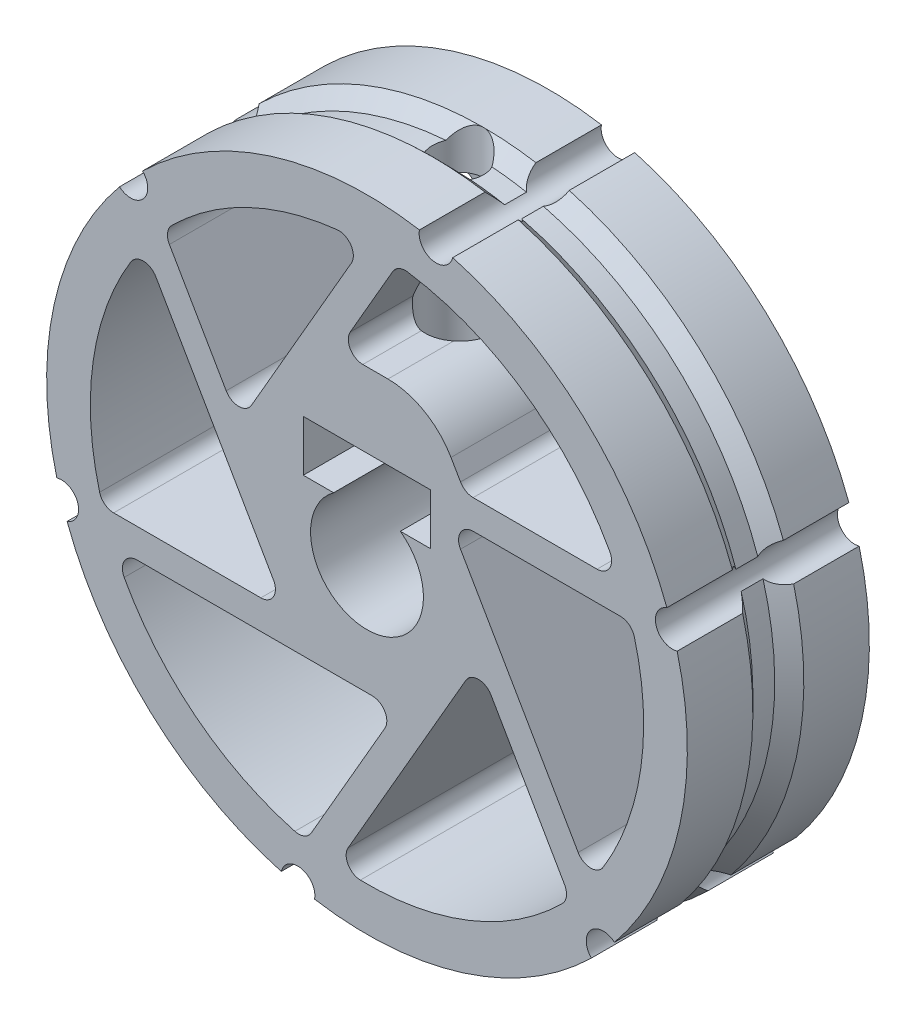
SolidWorks part; units mm, degrees
ref_plane "Front Plane" through (0, 0, 0) normal (0, 0, 1) x (1, 0, 0)
ref_plane "Top Plane" through (0, 0, 0) normal (0, 1, 0) x (1, 0, 0)
ref_plane "Right Plane" through (0, 0, 0) normal (1, 0, 0) x (0, 0, -1)
sketch "Sketch1" plane through (0, 0, 0) normal (0, 0, 1) x (1, 0, 0)
  line L0 (1.833, 2.5) -> (3.5, 2.5)
  line L1 (3.5, 2.5) -> (3.5, 5.3)
  line L2 (3.5, 5.3) -> (-3.5, 5.3)
  line L3 (-3.5, 5.3) -> (-3.5, 2.5)
  line L4 (-3.5, 2.5) -> (-1.833, 2.5)
  line L5 (-1.6583, 2.5) -> (1.6583, 2.5) construction
  line L6 (-7.0437, 0) -> (-12.2439, 9.0071)
  line L7 (3.5218, -6.1) -> (7.0437, 0) construction
  line L8 (7.0437, 0) -> (3.5218, 6.1) construction
  line L9 (3.5218, 6.1) -> (-3.5218, 6.1) construction
  line L10 (-3.5218, 6.1) -> (-7.0437, 0) construction
  line L11 (-7.0437, 0) -> (-3.5218, -6.1) construction
  line L12 (-3.5218, -6.1) -> (3.5218, -6.1) construction
  line L13 (-3.5218, -6.1) -> (-13.9223, -6.1)
  line L14 (3.5218, -6.1) -> (-1.6784, -15.1071)
  line L15 (7.0437, 0) -> (12.2439, -9.0071)
  line L16 (-6.1199, 1.6) -> (-11.1564, 10.3235) construction
  line L17 (6.1199, -1.6) -> (11.1564, -10.3235)
  line L18 (1.6743, -6.1) -> (-3.3622, -14.8235)
  line L19 (-4.4456, -4.5) -> (-14.5186, -4.5)
  line L20 (3.5218, 6.1) -> (13.9223, 6.1) construction
  line L21 (4.4456, 4.5) -> (14.5186, 4.5)
  line L22 (-11.1564, 10.3235) -> (-7.0437, 3.2)
  line L23 (-7.0437, 3.2) -> (-3.4613, 9.4048)
  line L24 (-3.4613, 9.4048) -> (3.4613, 9.4048) construction
  line L25 (3.4613, 9.4048) -> (5.3694, 6.1)
  line L26 (5.3694, 6.1) -> (13.9223, 6.1)
  line L29 (-7.0437, 0) -> (-4.4456, -4.5)
  line L30 (-3.5218, -6.1) -> (1.6743, -6.1)
  line L31 (3.5218, -6.1) -> (6.1199, -1.6)
  line L32 (7.0437, 0) -> (4.4456, 4.5)
  line L33 (-3.4613, 9.4048) -> (-0.1157, 15.1996)
  line L34 (1.6784, 15.1071) -> (-1.6138, 9.4048)
  line L35 (3.4613, 9.4048) -> (-1.6138, 9.4048)
  circle A0 centre (0, 0) radius 3 construction
  circle A1 centre (0, 0) radius 3.1 construction
  arc A2 (-1.833, 2.5) -> (1.833, 2.5) centre (0, 0) ccw
  circle A3 centre (0, 0) radius 6.1 construction
  circle A4 centre (0, 0) radius 20 construction
  circle A6 centre (0, 0) radius 17.6
  circle A7 centre (0, 0) radius 15.2 construction
  arc A8 (-0.1157, 15.1996) -> (-11.1564, 10.3235) centre (0, 0) ccw
  arc A9 (-12.2439, 9.0071) -> (-14.5186, -4.5) centre (0, 0) ccw
  arc A10 (-3.3622, -14.8235) -> (-13.9223, -6.1) centre (0, 0) cw
  arc A11 (11.1564, -10.3235) -> (-1.6784, -15.1071) centre (0, 0) cw
  arc A12 (14.5186, 4.5) -> (12.2439, -9.0071) centre (0, 0) cw
  arc A13 (13.9223, 6.1) -> (1.6784, 15.1071) centre (0, 0) ccw
  point P13 (0, -3)
  point P43 (0, 9.4048)
  point P55 (-17.6, 0)
  point P56 (17.6, 0)
  point P58 (0, -17.6)
  point P59 (0, 17.6)
  point P61 (-15.2, 0)
  dimension "D1" = 6
  dimension "D7" = 40
  dimension "D3" = 7
  dimension "D4" = 2.8
  dimension "D5" = 5.5
  dimension "D6" = 0.8
  dimension "D10" = 1.6
  dimension "D11" = 4.1048
  dimension "D12" = 1.6
  dimension "D13" = 1.6
  dimension "D2" = 0.1
  dimension "D8" = 2.4
  dimension "D9" = 2.4
extrude "Boss-Extrude1" add sketch "Sketch1" along normal blind 10
ref_axis "Axis1" through (0, 0, 10) along (0, 0, -1)
sketch "Sketch3" plane through (0, 0, 10) normal (0, 0, 1) x (1, 0, 0)
  line L0 (2.5981, -6.1) -> (-3.8016, -17.1845) construction
  line L1 (-3.5218, -6.1) -> (3.5218, -6.1) construction
  line L2 (1.6743, -6.1) -> (-3.3622, -14.8235) construction
  line L3 (1.6743, -6.1) -> (3.5218, -6.1) construction
  circle A0 centre (-3.8016, -17.1845) radius 0.937
  circle A1 centre (0, 0) radius 17.6 construction
  circle A2 centre (0, 0) radius 15.2 construction
  circle A3 centre (-16.783, -5.3) radius 0.937
  circle A4 centre (-12.9814, 11.8845) radius 0.937
  circle A5 centre (3.8016, 17.1845) radius 0.937
  circle A6 centre (16.783, 5.3) radius 0.937
  circle A7 centre (12.9814, -11.8845) radius 0.937
  point P14 (2.5981, -6.1)
  point P15 (-3.3331, -16.3731)
  point P16 (-2.5331, -14.9874)
  point P32 (0, 0)
  dimension "D1" = 1.6
  dimension "D2" = 6
extrude "Cut-Extrude2" cut sketch "Sketch3" against normal through all
fillet "Fillet1" radius 0.8 7 edges at (4.4456, 4.5, 5) (6.1199, -1.6, 5) (1.6743, -6.1, 5) (-4.4456, -4.5, 5) (-7.0437, 3.2, 5) (-1.6138, 9.4048, 5) (5.3694, 6.1, 5)
fillet "Fillet2" radius 0.8 6 edges at (12.2439, -9.0071, 5) (13.9223, 6.1, 5) (-12.2439, 9.0071, 5) (-13.9223, -6.1, 5) (-1.6784, -15.1071, 5) (-0.1157, 15.1996, 5)
fillet "Fillet3" radius 0.8 6 edges at (-14.5186, -4.5, 5) (-11.1564, 10.3235, 5) (14.5186, 4.5, 5) (11.1564, -10.3235, 5) (-3.3622, -14.8235, 5) (1.6784, 15.1071, 5)
sketch "Sketch2" plane through (0, 5.3, 0) normal (0, -1, 0) x (1, 0, 0)
  line L0 (0, 10) -> (0, 0) construction
  line L1 (3.5, 10) -> (-3.5, 10) construction
  line L2 (3.5, 0) -> (-3.5, 0) construction
  circle A0 centre (0, 5) radius 1.8
  dimension "D1" = 3.6
extrude "Cut-Extrude1" cut sketch "Sketch2" against normal up to surface (9.793 mm away) up to face at (8.2376, 11.8142, 5)
sketch "Sketch6" plane through (0, 5.3, 0) normal (0, -1, 0) x (1, 0, 0)
  circle A0 centre (0, 5) radius 1.4
  dimension "D1" = 2.8
extrude "Cut-Extrude3" cut sketch "Sketch6" against normal through all
fillet "Fillet4" radius 4 1 edges at (3.4613, 9.4048, 5)
sketch "Sketch5" plane through (0, 0, 0) normal (0, 1, 0) x (1, 0, 0)
  line L0 (-17.6, -3.6) -> (-17.6, -6.4)
  line L3 (-17.6, -3.6) -> (-16.8, -4.4)
  line L4 (-16.8, -4.4) -> (-16.8, -5.6)
  line L5 (-16.8, -5.6) -> (-17.6, -6.4)
  point P3 (-17.6, -5)
  dimension "D1" = 1.6
  dimension "D2" = 45
  dimension "D3" = 1.2
revolve "Cut-Revolve1" cut sketch "Sketch5" angle 360 about axis through (0, 0, 10) along (0, 0, -1)
